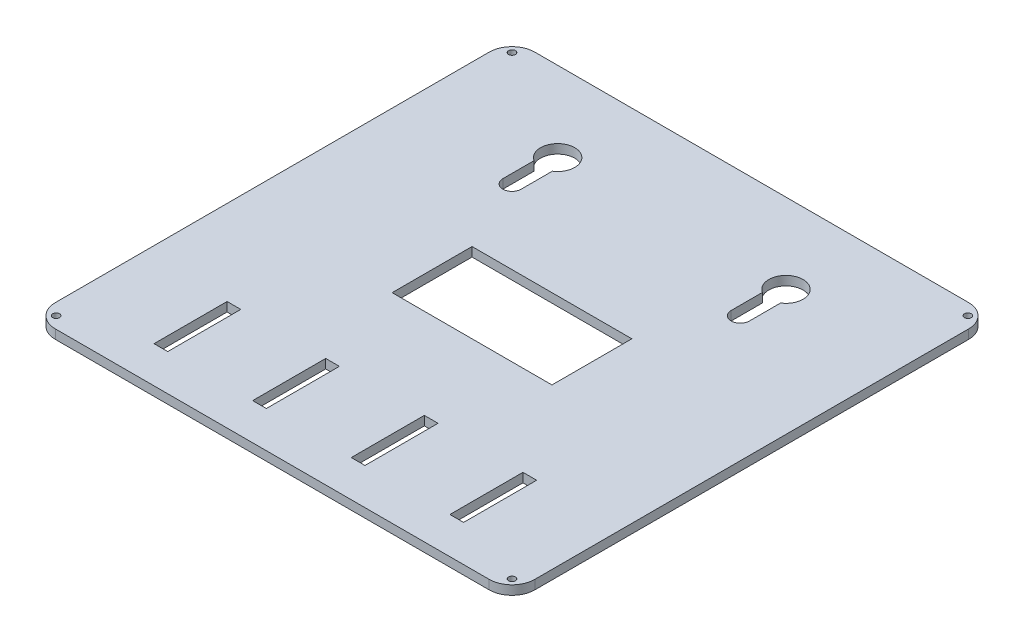
SolidWorks part; units mm, degrees
ref_plane "Front Plane" through (0, 0, 0) normal (0, 0, 1) x (1, 0, 0)
ref_plane "Top Plane" through (0, 0, 0) normal (0, 1, 0) x (1, 0, 0)
ref_plane "Right Plane" through (0, 0, 0) normal (1, 0, 0) x (0, 0, -1)
sketch "Sketch1" plane through (0, 0, 0) normal (0, 1, 0) x (1, 0, 0)
  line L0 (-101, -101) -> (-101, 101)
  line L5 (-105, -105) -> (105, -105)
  line L6 (-105, -105) -> (-105, 105)
  line L7 (-105, 105) -> (105, 105)
  line L8 (105, -105) -> (105, 105)
  line L9 (-101, 101) -> (101, 101)
  line L10 (101, -101) -> (101, 101)
  line L11 (-101, -101) -> (101, -101)
  line L12 (-101, 101) -> (-99.8333, 99.8333) construction
  line L13 (-55, 0) -> (55, 0) construction
  line L14 (-101, -101) -> (-99.8333, -99.8333) construction
  line L15 (0, -55) -> (0, 55) construction
  line L16 (101, -101) -> (99.8333, -99.8333) construction
  line L17 (101, 101) -> (99.8333, 99.8333) construction
  circle A1 centre (-99.8333, 99.8333) radius 1.5
  circle A2 centre (-99.8333, -99.8333) radius 1.5
  circle A3 centre (99.8333, -99.8333) radius 1.5
  circle A4 centre (99.8333, 99.8333) radius 1.5
  point P0 (0, 0)
  point P6 (-105, 0)
  point P7 (0, 105)
  dimension "D3" = 4
  dimension "D4" = 3
  dimension "D1" = 210
  dimension "D2" = 210
  dimension "D5" = 1.65
  dimension "D6" = 45
extrude "MainExtrude" add sketch "Sketch1" along normal mid plane 4 contours L6 L5 L8 L7
extrude "ScrewHoles" cut sketch "Sketch1<6>" along normal mid plane 4 contours A1 | A2 | A3 | A4
sketch "Sketch1<6>" plane through (0, 0, 0) normal (0, 1, 0) x (1, 0, 0) same geometry as "Sketch1"
fillet "RoundedCorners" radius 10 4 edges at (-105, 0, -105) (-105, 0, 105) (105, 0, -105) (105, 0, 105)
sketch "Sketch2" plane through (0, 2, 0) normal (0, 1, 0) x (1, 0, 0)
  line L0 (-50, 70) -> (-50, 50) construction
  line L1 (-67.8, -57) -> (-61.8, -57)
  line L2 (-67.8, -57) -> (-67.8, -89)
  line L3 (-67.8, -89) -> (-61.8, -89)
  line L4 (-61.8, -57) -> (-61.8, -89)
  line L5 (-24.6, -57) -> (-18.6, -57)
  line L6 (-24.6, -57) -> (-24.6, -89)
  line L7 (-24.6, -89) -> (-18.6, -89)
  line L8 (-18.6, -57) -> (-18.6, -89)
  line L9 (18.6, -57) -> (24.6, -57)
  line L10 (18.6, -57) -> (18.6, -89)
  line L11 (18.6, -89) -> (24.6, -89)
  line L12 (24.6, -57) -> (24.6, -89)
  line L13 (61.8, -57) -> (67.8, -57)
  line L14 (61.8, -57) -> (61.8, -89)
  line L15 (61.8, -89) -> (67.8, -89)
  line L16 (67.8, -57) -> (67.8, -89)
  line L17 (-95, -105) -> (95, -105) construction
  line L19 (-67.8, -57) -> (-105, -57) construction
  line L20 (-105, -95) -> (-105, 95) construction
  line L21 (-61.8, -57) -> (-24.6, -57) construction
  line L22 (-18.6, -57) -> (18.6, -57) construction
  line L23 (24.6, -57) -> (61.8, -57) construction
  line L25 (-105, 60) -> (-50, 60) construction
  line L26 (-95, 105) -> (95, 105) construction
  line L30 (-54, 50) -> (-54, 63.6557)
  line L31 (-46, 50) -> (-46, 63.6557)
  line L32 (0, -2.2) -> (0, 2.2) construction
  line L33 (46, 50) -> (46, 63.6557)
  line L34 (54, 50) -> (54, 63.6557)
  line L36 (35, -17.5) -> (-35, -17.5)
  line L37 (35, -17.5) -> (35, 17.5)
  line L38 (35, 17.5) -> (-35, 17.5)
  line L39 (-35, -17.5) -> (-35, 17.5)
  arc A0 (-54, 50) -> (-46, 50) centre (-50, 50) ccw
  arc A4 (-46, 63.6557) -> (-54, 63.6557) centre (-50, 70) ccw
  arc A5 (54, 50) -> (46, 50) centre (50, 50) cw
  arc A6 (46, 63.6557) -> (54, 63.6557) centre (50, 70) cw
  point P30 (0, 17.5)
  point P40 (-50, 60)
  point P42 (0, 0)
  point P48 (-35, 0)
  dimension "D7" = 15
  dimension "D8" = 4
  dimension "D1" = 6
  dimension "D2" = 32
  dimension "D3" = 37.2
  dimension "D4" = 16
  dimension "D5" = 55
  dimension "D6" = 45
  dimension "D9" = 20
  dimension "D10" = 70
  dimension "D11" = 35
  dimension "D12" = 50
  dimension "D13" = 50
extrude "Knotches/Sliders" cut sketch "Sketch2" against normal up to surface (4 mm away) up to face at (-99.8333, -2, 98.3333)
